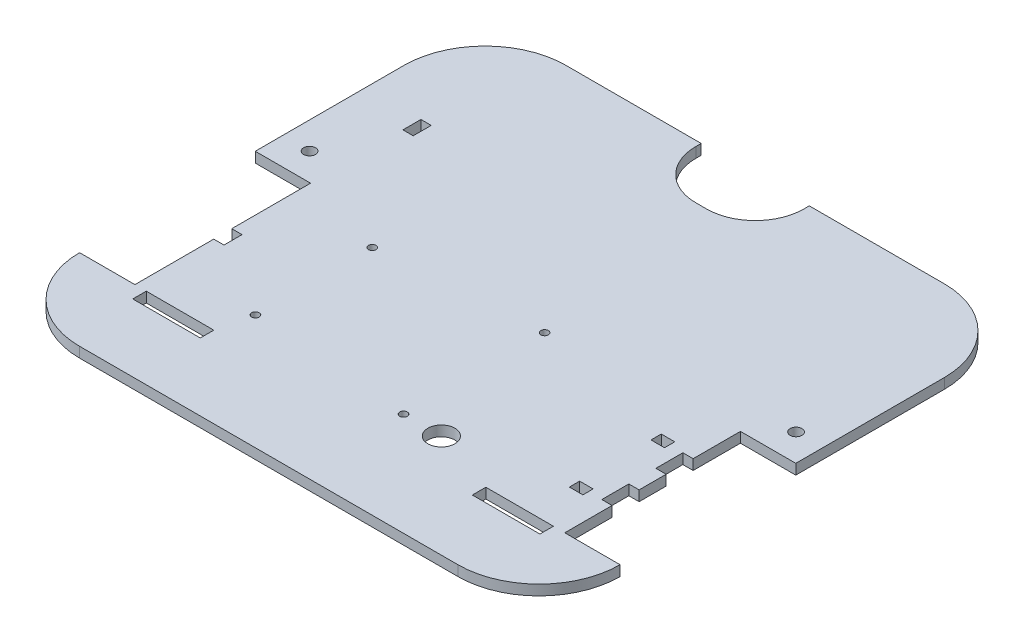
SolidWorks part; units mm, degrees
ref_plane "Front Plane" through (0, 0, 0) normal (0, 0, 1) x (1, 0, 0)
ref_plane "Top Plane" through (0, 0, 0) normal (0, 1, 0) x (1, 0, 0)
ref_plane "Right Plane" through (0, 0, 0) normal (1, 0, 0) x (0, 0, -1)
sketch "Sketch1" plane through (0, 0, 0) normal (0, 1, 0) x (1, 0, 0)
  line L1 (-127, 114.3) -> (127, 114.3)
  line L2 (-127, 114.3) -> (-127, -114.3)
  line L3 (-127, -114.3) -> (127, -114.3)
  line L4 (127, 114.3) -> (127, -114.3)
  line L5 (-127, 114.3) -> (127, -114.3) construction
  line L6 (-127, -114.3) -> (127, 114.3) construction
  point P0 (0, 0)
  dimension "D1" = 254
  dimension "D2" = 228.6
extrude "Boss-Extrude1" add sketch "Sketch1" along normal blind 4.826
sketch "Sketch2" plane through (0, 4.826, 0) normal (0, 1, 0) x (1, 0, 0)
  line L0 (-127, 114.3) -> (-127, -114.3) construction
  line L1 (-127, 6.35) -> (-101, 6.35)
  line L2 (-127, 6.35) -> (-127, -76.2)
  line L3 (-127, -76.2) -> (-101, -76.2)
  line L4 (-101, 6.35) -> (-101, -76.2)
  line L5 (127, -114.3) -> (127, 114.3) construction
  line L6 (127, 6.35) -> (101, 6.35)
  line L7 (127, 6.35) -> (127, -76.2)
  line L8 (127, -76.2) -> (101, -76.2)
  line L9 (101, 6.35) -> (101, -76.2)
  line L10 (-127, -114.3) -> (127, -114.3) construction
  dimension "D1" = 38.1
  dimension "D2" = 38.1
  dimension "D3" = 82.55
  dimension "D4" = 82.55
  dimension "D5" = 26
  dimension "D6" = 26
extrude "Cut-Extrude1" cut sketch "Sketch2" against normal blind 4.826
sketch "Sketch4" plane through (0, 4.826, 0) normal (0, 1, 0) x (1, 0, 0)
  line L0 (0, -114.3) -> (0, 114.3) construction
  line L1 (-127, -114.3) -> (127, -114.3) construction
  line L2 (127, 114.3) -> (-127, 114.3) construction
  line L3 (-127, 76.2) -> (-88.9, 76.2) construction
  line L4 (-127, 114.3) -> (-127, 6.35) construction
  line L5 (-88.9, 76.2) -> (-88.9, 114.3) construction
  line L6 (-127, 76.2) -> (-127, 114.3)
  line L7 (-127, 114.3) -> (-88.9, 114.3)
  line L8 (127, 76.2) -> (127, 114.3)
  line L9 (127, 114.3) -> (88.9, 114.3)
  arc A0 (-127, 76.2) -> (-88.9, 114.3) centre (-88.9, 76.2) cw
  arc A1 (127, 76.2) -> (88.9, 114.3) centre (88.9, 76.2) ccw
  dimension "D1" = 38.1
  dimension "D2" = 38.1
extrude "Cut-Extrude3" cut sketch "Sketch4" against normal blind 4.826
sketch "Sketch7" plane through (0, 4.826, 0) normal (0, 1, 0) x (1, 0, 0)
  line L0 (0, -114.3) -> (0, 114.3) construction
  line L1 (-127, -114.3) -> (127, -114.3) construction
  line L2 (88.9, 114.3) -> (-88.9, 114.3) construction
  line L3 (25.4, 88.9) -> (25.4, 114.3)
  line L4 (25.4, 88.9) -> (-25.4, 88.9)
  line L5 (0, 88.9) -> (0, 114.3)
  line L6 (25.4, 114.3) -> (-25.4, 114.3)
  line L7 (-25.4, 88.9) -> (-25.4, 114.3)
  line M6 (88.9, 114.3) -> (-88.9, 114.3)
extrude "Cut-Extrude5" cut sketch "Sketch7" against normal blind 4.826 contours L7 L4 L5 M6 | L5 L4 L3 M6 region at (12.7, 4.826, -101.6) region at (-12.7, 4.826, -101.6)
fillet "Fillet9" radius 22.86 1 edges at (-25.4, 2.413, -88.9) type face fillet first side face at (0, 2.413, -88.9) second side face at (-25.4, 2.413, -101.6)
fillet "Fillet10" radius 22.86 1 edges at (25.4, 2.413, -88.9) type face fillet first side face at (11.43, 2.413, -88.9) second side face at (25.4, 2.413, -101.6)
sketch "Sketch8" plane through (0, 4.826, 0) normal (0, 1, 0) x (1, 0, 0)
  line L0 (-127, -76.2) -> (-88.9, -76.2) construction
  line L1 (-88.9, -76.2) -> (-88.9, -114.3) construction
  line L2 (-127, -114.3) -> (127, -114.3) construction
  line L3 (-127, -76.2) -> (-127, -114.3)
  line L4 (-127, -114.3) -> (-88.9, -114.3)
  line L5 (0, -114.3) -> (0, 88.9) construction
  line L6 (2.54, 88.9) -> (-2.54, 88.9) construction
  line L7 (127, -114.3) -> (88.9, -114.3)
  line L8 (127, -76.2) -> (127, -114.3)
  arc A0 (-127, -76.2) -> (-88.9, -114.3) centre (-88.9, -76.2) ccw
  arc A1 (127, -76.2) -> (88.9, -114.3) centre (88.9, -76.2) cw
  dimension "D1" = 38.1
extrude "Cut-Extrude6" cut sketch "Sketch8" against normal blind 4.826
sketch "Sketch9" plane through (0, 0, 0) normal (0, -1, 0) x (1, 0, 0)
  line L0 (-58.582, 76.2) -> (-101, 76.2) construction
  line L1 (-95.666, 76.2) -> (-63.916, 76.2)
  line L2 (-95.666, 76.2) -> (-95.666, 82.55)
  line L3 (-95.666, 82.55) -> (-63.916, 82.55)
  line L4 (-63.916, 76.2) -> (-63.916, 82.55)
  line L5 (-101, 76.2) -> (-95.666, 76.2) construction
  line L6 (-63.916, 76.2) -> (-58.582, 76.2) construction
  line L7 (0, 114.3) -> (0, -88.9) construction
  line L8 (-88.9, 114.3) -> (88.9, 114.3) construction
  line L9 (2.54, -88.9) -> (-2.54, -88.9) construction
  line L10 (63.916, 76.2) -> (58.582, 76.2) construction
  line L11 (101, 76.2) -> (95.666, 76.2) construction
  line L12 (63.916, 76.2) -> (63.916, 82.55)
  line L13 (95.666, 82.55) -> (63.916, 82.55)
  line L14 (95.666, 76.2) -> (95.666, 82.55)
  line L15 (95.666, 76.2) -> (63.916, 76.2)
  dimension "D1" = 31.75
  dimension "D2" = 6.35
extrude "Cut-Extrude7" cut sketch "Sketch9" against normal through all
sketch "Sketch17" plane through (0, 0, 0) normal (0, -1, 0) x (1, 0, 0)
  circle A0 centre (114.3, -19.1646) radius 2.7781 construction
  circle A1 centre (-114.3, -19.1646) radius 2.7781 construction
  circle A2 centre (114.3, -19.1646) radius 2.7781
  circle A3 centre (-114.3, -19.1646) radius 2.7781
extrude "Cut-Extrude14" cut sketch "Sketch17" against normal through all
sketch "Sketch18" plane through (0, 4.826, 0) normal (0, 1, 0) x (1, 0, 0)
  line L0 (101, -53.975) -> (96.174, -53.975) construction
  line L1 (96.174, -41.275) -> (96.174, -53.975) construction
  line L2 (101, -41.275) -> (96.174, -41.275) construction
  line L3 (101, -41.275) -> (101, -53.975) construction
  line L4 (101, -15.875) -> (101, -28.575) construction
  line L5 (101, -15.875) -> (96.174, -15.875) construction
  line L6 (96.174, -15.875) -> (96.174, -28.575) construction
  line L7 (101, -28.575) -> (96.174, -28.575) construction
  line L8 (101, -53.975) -> (96.174, -53.975)
  line L9 (96.174, -41.275) -> (96.174, -53.975)
  line L10 (101, -41.275) -> (96.174, -41.275)
  line L11 (101, -41.275) -> (101, -53.975)
  line L12 (101, -15.875) -> (101, -28.575)
  line L13 (101, -15.875) -> (96.174, -15.875)
  line L14 (96.174, -15.875) -> (96.174, -28.575)
  line L15 (101, -28.575) -> (96.174, -28.575)
extrude "Cut-Extrude15" cut sketch "Sketch18" against normal through all
sketch "Sketch19" plane through (0, 4.826, 0) normal (0, 1, 0) x (1, 0, 0)
  line L0 (-101, -39.1583) -> (-101, -30.6917) construction
  line L1 (-101, -39.1583) -> (-96.174, -39.1583) construction
  line L2 (-96.174, -39.1583) -> (-96.174, -30.6917) construction
  line L3 (-101, -30.6917) -> (-96.174, -30.6917) construction
  line L4 (-101, 49.7417) -> (-101, 58.2083) construction
  line L5 (-101, 49.7417) -> (-96.174, 49.7417) construction
  line L6 (-96.174, 49.7417) -> (-96.174, 58.2083) construction
  line L7 (-101, 58.2083) -> (-96.174, 58.2083) construction
  line L8 (-101, -39.1583) -> (-101, -30.6917)
  line L9 (-101, -39.1583) -> (-96.174, -39.1583)
  line L10 (-96.174, -39.1583) -> (-96.174, -30.6917)
  line L11 (-101, -30.6917) -> (-96.174, -30.6917)
  line L12 (-101, 49.7417) -> (-101, 58.2083)
  line L13 (-101, 49.7417) -> (-96.174, 49.7417)
  line L14 (-96.174, 49.7417) -> (-96.174, 58.2083)
  line L15 (-101, 58.2083) -> (-96.174, 58.2083)
extrude "Cut-Extrude16" cut sketch "Sketch19" against normal through all
sketch "Sketch20" plane through (0, 0, 0) normal (0, -1, 0) x (1, 0, 0)
  line L0 (83.474, 51.689) -> (89.824, 51.689) construction
  line L1 (83.474, 56.515) -> (83.474, 51.689) construction
  line L2 (83.474, 56.515) -> (89.824, 56.515) construction
  line L3 (89.824, 56.515) -> (89.824, 51.689) construction
  line L4 (83.474, 13.335) -> (89.824, 13.335) construction
  line L5 (83.474, 18.161) -> (83.474, 13.335) construction
  line L6 (83.474, 18.161) -> (89.824, 18.161) construction
  line L7 (89.824, 18.161) -> (89.824, 13.335) construction
  line L8 (83.474, 51.689) -> (89.824, 51.689)
  line L9 (83.474, 56.515) -> (83.474, 51.689)
  line L10 (83.474, 56.515) -> (89.824, 56.515)
  line L11 (89.824, 56.515) -> (89.824, 51.689)
  line L12 (83.474, 13.335) -> (89.824, 13.335)
  line L13 (83.474, 18.161) -> (83.474, 13.335)
  line L14 (83.474, 18.161) -> (89.824, 18.161)
  line L15 (89.824, 18.161) -> (89.824, 13.335)
extrude "Cut-Extrude17" cut sketch "Sketch20" against normal blind 4.826
sketch "Sketch21" plane through (0, 4.826, 0) normal (0, 1, 0) x (1, 0, 0)
  circle A0 centre (-60.3522, -60.2197) radius 1.778 construction
  circle A1 centre (-60.3522, -5.3557) radius 1.778 construction
  circle A2 centre (14.8318, -65.8077) radius 1.778 construction
  circle A3 centre (14.8318, 0.4863) radius 1.778 construction
  circle A4 centre (-60.3522, -60.2197) radius 1.778
  circle A5 centre (-60.3522, -5.3557) radius 1.778
  circle A6 centre (14.8318, -65.8077) radius 1.778
  circle A7 centre (14.8318, 0.4863) radius 1.778
extrude "Cut-Extrude18" cut sketch "Sketch21" against normal through all
sketch "Sketch22" plane through (0, 4.826, 0) normal (0, 1, 0) x (1, 0, 0)
  circle A0 centre (32.6118, -65.8077) radius 6.35
  circle A1 centre (14.8318, -65.8077) radius 1.778 construction
  dimension "D1" = 12.7
  dimension "D2" = 17.78
extrude "Cut-Extrude19" cut sketch "Sketch22" against normal through all
equation "\"MDF\"= 0.19in"
equation "\"GenDiameter\"= 60mm"
equation "\"GenCutDiameter\" = 1.8in"
equation "\"GenCutDistance\" = 1"
equation "\"TowerHeight\" = 6in"
equation "\"TowerFrontBase\" = 3in"
equation "\"FunnelHeight\" = 1in"
equation "\"FunnelAngle\" = 20"
equation "\"TowerSideBase\" = 3in"
equation "\"BaseLength\" = 9in"
equation "\"BaseWidth\" = 10in"
equation "\"WheelHoleLength\" = 3.25in"
equation "\"WheelHoleWidth\" = 26mm"
equation "\"DropLength\" = 1in"
equation "\"D1@Sketch1\"=\"BaseWidth\""
equation "\"D2@Sketch1\"=\"BaseLength\""
equation "\"D1@Boss-Extrude1\"=\"MDF\""
equation "\"WheelHoleFromBack\" = 1.5in"
equation "\"D1@Sketch2\"=\"WheelHoleFromBack\""
equation "\"D2@Sketch2\"=\"WheelHoleFromBack\""
equation "\"D3@Sketch2\"=\"WheelHoleLength\""
equation "\"D4@Sketch2\"=\"WheelHoleLength\""
equation "\"D5@Sketch2\"=\"WheelHoleWidth\""
equation "\"D6@Sketch2\"=\"WheelHoleWidth\""
equation "\"D1@Cut-Extrude1\"=\"MDF\""
equation "\"DropWidth\" = 8.5in"
equation "\"BumperWidth\" = 2in"
equation "\"D1@Cut-Extrude3\"=\"MDF\""
equation "\"D1@Sketch7\"=\"DropLength\""
equation "\"D1@Cut-Extrude5\"=\"MDF\""
equation "\"D1@Cut-Extrude6\"=\"MDF\""
equation "\"DropWidthTop\" = 0in"
equation "\"D1@Cut-Extrude17\"=\"MDF\""
